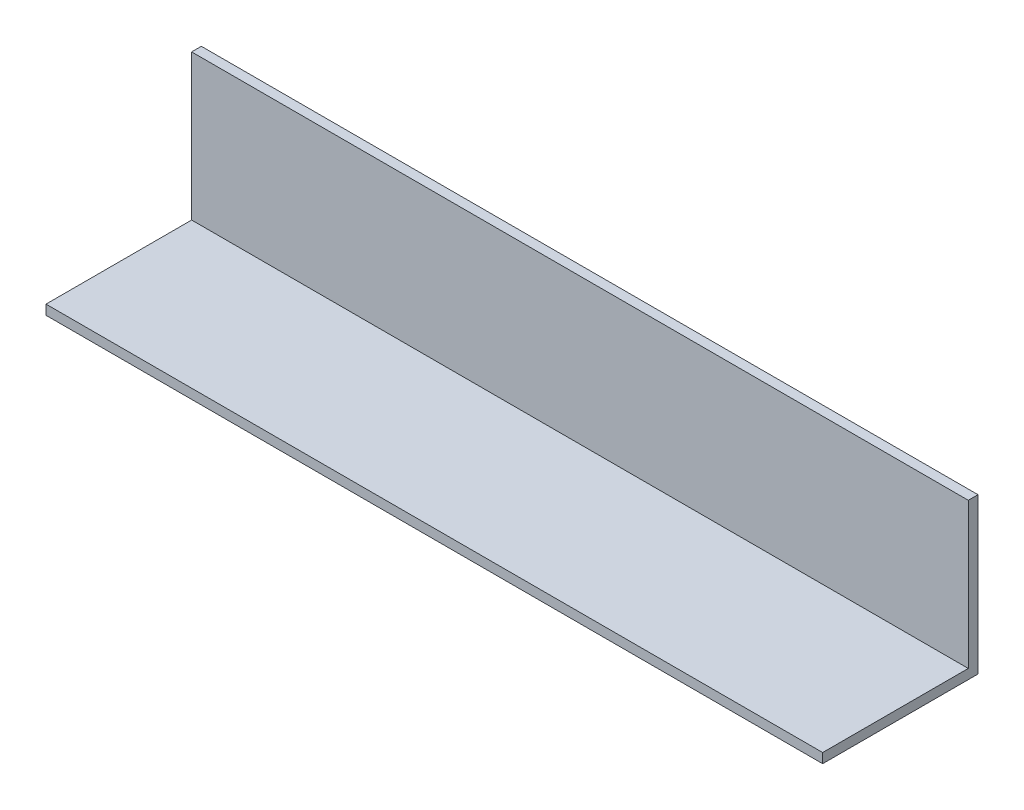
SolidWorks part; units mm, degrees
ref_plane "Front Plane" through (0, 0, 0) normal (0, 0, 1) x (1, 0, 0)
ref_plane "Top Plane" through (0, 0, 0) normal (0, 1, 0) x (1, 0, 0)
ref_plane "Right Plane" through (0, 0, 0) normal (1, 0, 0) x (0, 0, -1)
sketch "Sketch1" plane through (0, 0, 0) normal (1, 0, 0) x (0, 0, -1)
  line L1 (-3.175, 0) -> (-50.8, 0)
  line L2 (0, 0) -> (0, -3.175)
  line L3 (0, -3.175) -> (-50.8, -3.175)
  line L4 (-50.8, 0) -> (-50.8, -3.175)
  line L6 (0, 0) -> (0, 47.625)
  line L7 (0, 47.625) -> (-3.175, 47.625)
  line L8 (-3.175, 0) -> (-3.175, 47.625)
  dimension "D1" = 3.175
  dimension "D2" = 50.8
  dimension "D3" = 50.8
  dimension "D4" = 3.175
extrude "Boss-Extrude1" add sketch "Sketch1" along normal blind 254
